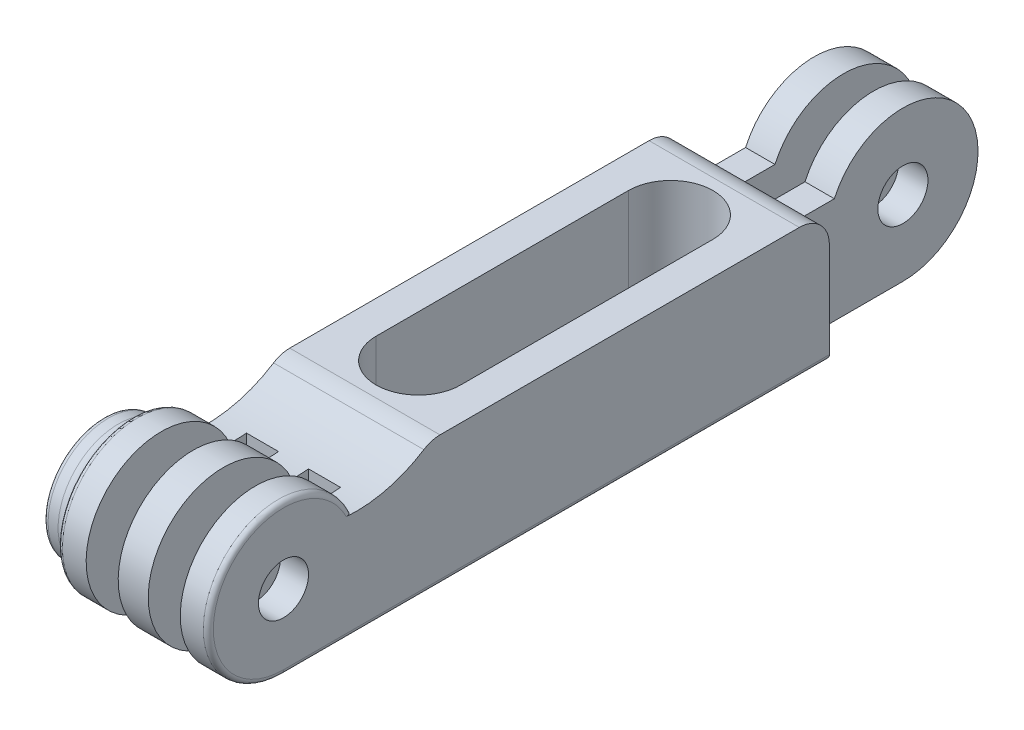
SolidWorks part; units mm, degrees
ref_plane "Ön Düzlem" through (0, 0, 0) normal (0, 0, 1) x (1, 0, 0)
ref_plane "Üst Düzlem" through (0, 0, 0) normal (0, 1, 0) x (1, 0, 0)
ref_plane "Sağ Düzlem" through (0, 0, 0) normal (1, 0, 0) x (0, 0, -1)
sketch "Çizim1" plane through (0, 0, 0) normal (0, 0, 1) x (1, 0, 0)
  line L0 (0, 0) -> (15, 0)
  line L1 (15, 0) -> (15, 15)
  line L2 (15, 15) -> (0, 15)
  line L3 (0, 15) -> (0, 0)
extrude "Yükseklik-Ekstrüzyon1" add sketch "Çizim1" along normal blind 80
sketch "Çizim2" plane through (0, 15, 0) normal (0, 1, 0) x (1, 0, 0)
  line L0 (0, 0) -> (2.98, 0)
  line L1 (15, 0) -> (0, 0) construction
  line L2 (2.98, 0) -> (5.91, 0)
  line L3 (5.91, 0) -> (8.91, 0)
  line L4 (8.91, 0) -> (11.84, 0)
  line L5 (11.84, 0) -> (15, 0)
  line L6 (2.98, 0) -> (2.98, -18)
  line L7 (2.98, -18) -> (0, -18)
  line L8 (0, -80) -> (0, 0) construction
  line L9 (5.91, 0) -> (5.91, -18)
  line L10 (8.91, 0) -> (8.91, -18)
  line L11 (11.84, 0) -> (11.84, -18)
  line L12 (11.84, -18) -> (15, -18)
  line L13 (15, -80) -> (15, 0) construction
  line L14 (5.91, -18) -> (8.91, -18)
  line L15 (15, -18) -> (15, 0)
  line L16 (0, 0) -> (0, -18)
  line M6 (15, 0) -> (0, 0)
  line M7 (0, 0) -> (0, -80)
  line M9 (15, -80) -> (15, 0)
extrude "Kes-Ekstrüzyon1" cut sketch "Çizim2" against normal blind 80 contours L7 L6 M6 M7 | L9 L14 L10 M6 | L11 L12 M9 M6 region at (13.42, 15, 9) region at (7.41, 15, 9) region at (1.49, 15, 9)
sketch "Çizim3" plane through (0, 15, 0) normal (0, 1, 0) x (1, 0, 0)
  line L0 (15, -80) -> (12.2, -80)
  line L1 (15, -80) -> (0, -80) construction
  line L2 (12.2, -80) -> (9, -80)
  line L3 (9, -80) -> (6, -80)
  line L4 (6, -80) -> (2.8, -80)
  line L5 (2.8, -80) -> (0, -80)
  line L6 (0, -80) -> (0, -64)
  line L7 (0, -80) -> (0, -18) construction
  line L8 (0, -64) -> (15, -64)
  line L9 (15, -80) -> (15, -18) construction
  line L10 (15, -64) -> (15, -80)
  line L11 (12.2, -80) -> (12.2, -64)
  line L12 (9, -80) -> (9, -64)
  line L13 (6, -80) -> (6, -64)
  line L14 (2.8, -80) -> (2.8, -64)
  line M11 (0, -80) -> (15, -80)
extrude "Kes-Ekstrüzyon2" cut sketch "Çizim3" against normal blind 80 contours L14 L13 L8 M11 | L12 L11 L8 M11 region at (10.6, 15, 72) region at (4.4, 15, 72)
sketch "Çizim4" plane through (15, 0, 0) normal (1, 0, 0) x (0, 0, -1)
  line L0 (-72.5, 15) -> (-80, 15)
  line L1 (-80, 15) -> (-80, 0)
  line L2 (-80, 0) -> (-72.5, 0)
  arc A0 (-72.5, 15) -> (-72.5, 0) centre (-72.5, 7.5) ccw
  circle A1 centre (-72.5, 7.5) radius 2.5
  line M1 (-80, 0) -> (-18, 0)
  line M3 (-18, 15) -> (-80, 15)
  line M4 (-80, 15) -> (-80, 0)
extrude "Kes-Ekstrüzyon3" cut sketch "Çizim4" against normal blind 80 contours A0 M3 M4 | A0 L1 M1 | A1 region at (15, 13.3247, 78.3247) region at (15, 1.6753, 78.3247) region at (15, 7.5, 72.5)
sketch "Çizim5" plane through (11.84, 0, 0) normal (1, 0, 0) x (0, 0, -1)
  line L0 (-7.5, 15) -> (0, 15)
  line L1 (0, 15) -> (0, 0)
  line L2 (0, 0) -> (-7.5, 0)
  arc A0 (-7.5, 0) -> (-7.5, 15) centre (-7.5, 7.5) ccw
  circle A1 centre (-7.5, 7.5) radius 2.5
  line M1 (0, 0) -> (0, 15)
  line M2 (0, 15) -> (-18, 15)
  line M4 (-18, 0) -> (0, 0)
extrude "Kes-Ekstrüzyon4" cut sketch "Çizim5" against normal blind 80 contours A0 L1 M2 | A0 M4 M1 | A1 region at (11.84, 1.6753, 1.6753) region at (11.84, 13.3247, 1.6753) region at (11.84, 7.5, 7.5)
sketch "Çizim6" plane through (0, 0, 0) normal (-1, 0, 0) x (0, 0, 1)
  circle A0 centre (72.5, 7.5) radius 6
  circle A1 centre (72.5, 7.5) radius 2.5
extrude "Yükseklik-Ekstrüzyon2" add sketch "Çizim6" along normal blind 3
sketch "Çizim7" plane through (-3, 0, 0) normal (-1, 0, 0) x (0, 0, 1)
  line L1 (77.9848, 7.5) -> (75.2424, 12.25)
  line L2 (75.2424, 12.25) -> (69.7576, 12.25)
  line L3 (69.7576, 12.25) -> (67.0152, 7.5)
  line L4 (67.0152, 7.5) -> (69.7576, 2.75)
  line L5 (69.7576, 2.75) -> (75.2424, 2.75)
  line L6 (75.2424, 2.75) -> (77.9848, 7.5)
extrude "Kes-Ekstrüzyon5" cut sketch "Çizim7" against normal blind 4
fillet "Radyus2" radius 0.5 1 edges at (-3, 7.5, 78.5)
fillet "Radyus3" radius 1.5 1 edges at (0, 7.5, 66.5)
sketch "Çizim8" plane through (15, 0, 0) normal (1, 0, 0) x (0, 0, -1)
  line L0 (-55.6571, 15) -> (-72.5, 15)
  line L4 (-72.5, 15) -> (-18, 15) construction
  arc A0 (-65.6571, 10.57) -> (-72.5, 15) centre (-72.5, 7.5) ccw
  arc A1 (-65.6571, 10.57) -> (-55.6571, 15) centre (-65.2308, 23.1093) ccw
extrude "Kes-Ekstrüzyon6" cut sketch "Çizim8" against normal blind 18
fillet "Radyus6" radius 0.5 2 edges at (0, 0, 45.25) (0, 11.5758, 78.7958)
fillet "Radyus7" radius 0.5 2 edges at (15, 0, 45.25) (15, 11.5758, 78.7958)
sketch "Çizim10" plane through (11.84, 0, 0) normal (1, 0, 0) x (0, 0, -1)
  line L0 (-18, 15) -> (-18, 10.57)
  line L1 (-18, 0) -> (-18, 15) construction
  line L2 (-18, 10.57) -> (-14.3429, 10.57)
  line L3 (-7.5, 15) -> (-18, 15)
  arc A0 (-7.5, 15) -> (-14.3429, 10.57) centre (-7.5, 7.5) ccw
extrude "Kes-Ekstrüzyon8" cut sketch "Çizim10" against normal blind 10
other "Move Face1" flip direction yes face at (7.5, 15, 36.8286) offset 2 parameters "D1"=2
fillet "Radyus8" radius 3 1 edges at (7.5, 13, 57.7999)
fillet "Radyus9" radius 3 1 edges at (7.5, 13, 18)
sketch "Çizim11" plane through (15, 0, 0) normal (1, 0, 0) x (0, 0, -1)
  text T0 "<b><i>       </i></b>\r\n<b><i>GoPro Arm</i></b>" font "Century Gothic" height 4.5
extrude "Kes-Ekstrüzyon9" [suppressed] cut sketch "Çizim11" against normal blind 1
sketch "Sketch1" plane through (0, 13, 0) normal (0, 1, 0) x (1, 0, 0)
  line L0 (0, -56.8737) -> (0, -21) construction
  line L1 (15, -21) -> (0, -21) construction
  line L2 (15, -21) -> (15, -56.8737) construction
  line L3 (15, -56.8737) -> (0, -56.8737) construction
  line L4 (0, -21) -> (0, -56.8737) construction
  line L5 (15, -21) -> (0, -56.8737) construction
  line L6 (15, -56.8737) -> (0, -21) construction
  line L7 (0, -56.8737) -> (0, -58.4863) construction
  line L8 (7.5, -26.344) -> (7.5, -51.5296) construction
  line L9 (11.7214, -26.344) -> (11.7214, -51.5296)
  line L10 (3.2786, -26.344) -> (3.2786, -51.5296)
  arc A0 (11.7214, -26.344) -> (3.2786, -26.344) centre (7.5, -26.344) ccw
  arc A1 (3.2786, -51.5296) -> (11.7214, -51.5296) centre (7.5, -51.5296) ccw
  point P4 (7.5, -38.9368)
  point P13 (7.5, -38.9368)
extrude "Cut-Extrude1" cut sketch "Sketch1" against normal through all both and the other way through all
